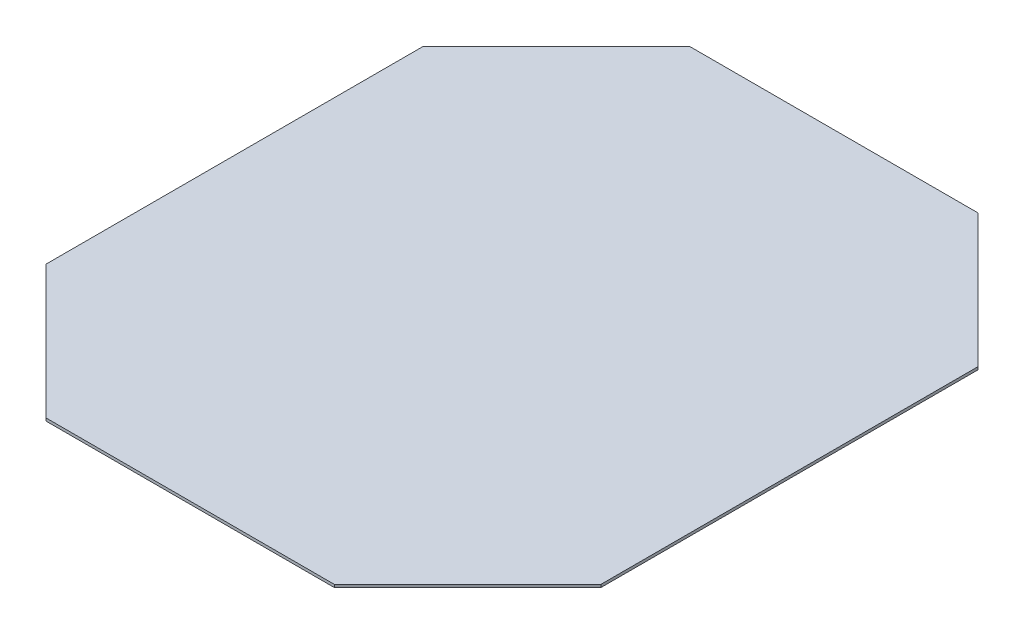
SolidWorks part; units mm, degrees
material "ABS PC"
ref_plane "Front Plane" through (0, 0, 0) normal (0, 0, 1) x (1, 0, 0)
ref_plane "Top Plane" through (0, 0, 0) normal (0, 1, 0) x (1, 0, 0)
ref_plane "Right Plane" through (0, 0, 0) normal (1, 0, 0) x (0, 0, -1)
sketch "Sketch1" plane through (0, 0, 0) normal (0, 1, 0) x (1, 0, 0)
  line L1 (-317.5, -368.3) -> (317.5, -368.3)
  line L2 (-317.5, -368.3) -> (-317.5, 368.3)
  line L3 (-317.5, 368.3) -> (317.5, 368.3)
  line L4 (317.5, -368.3) -> (317.5, 368.3)
  line L5 (-317.5, -368.3) -> (317.5, 368.3) construction
  line L6 (-317.5, 368.3) -> (317.5, -368.3) construction
  point P0 (0, 0)
  dimension "D1" = 635
  dimension "D2" = 736.6
extrude "Base" add sketch "Sketch1" along normal blind 3.175
sketch "Sketch2" plane through (0, 0, 0) normal (0, -1, 0) x (-1, 0, 0)
  line L0 (-317.5, 215.9) -> (-165.1, 368.3)
  line L1 (-317.5, -368.3) -> (-317.5, 368.3) construction
  line L2 (-317.5, 368.3) -> (317.5, 368.3) construction
  line L3 (165.1, 368.3) -> (317.5, 215.9)
  line L4 (317.5, 368.3) -> (317.5, -368.3) construction
  line L5 (317.5, -215.9) -> (165.1, -368.3)
  line L6 (317.5, -368.3) -> (-317.5, -368.3) construction
  line L7 (-317.5, -215.9) -> (-165.1, -368.3)
  line L8 (-165.1, 368.3) -> (-317.5, 368.3)
  line L9 (-317.5, 368.3) -> (-317.5, 215.9)
  line L10 (165.1, 368.3) -> (317.5, 368.3)
  line L11 (317.5, 368.3) -> (317.5, 215.9)
  line L12 (317.5, -215.9) -> (317.5, -368.3)
  line L13 (317.5, -368.3) -> (165.1, -368.3)
  line L14 (-317.5, -215.9) -> (-317.5, -368.3)
  line L15 (-317.5, -368.3) -> (-165.1, -368.3)
  dimension "D1" = 152.4
extrude "Module Cutout" cut sketch "Sketch2" against normal through all
